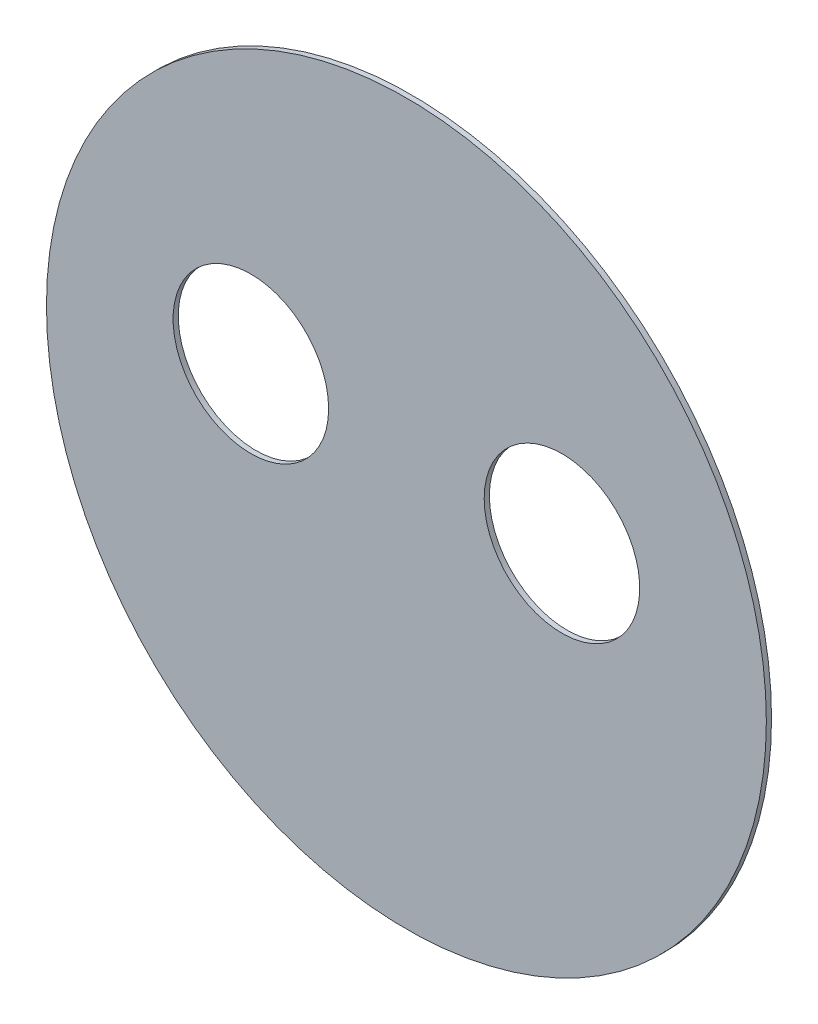
SolidWorks part; units mm, degrees
ref_plane "Front Plane" through (0, 0, 0) normal (0, 0, 1) x (1, 0, 0)
ref_plane "Top Plane" through (0, 0, 0) normal (0, 1, 0) x (1, 0, 0)
ref_plane "Right Plane" through (0, 0, 0) normal (1, 0, 0) x (0, 0, -1)
sketch "Sketch1" plane through (0, 0, 0) normal (0, 0, 1) x (1, 0, 0)
  circle A0 centre (0, 0) radius 34.7111
  dimension "D1" = 69.4222
extrude "Boss-Extrude1" add sketch "Sketch1" along normal blind 0.5 contours A0
sketch "Sketch3" plane through (0, 0, 0.5) normal (0, 0, 1) x (1, 0, 0)
  line L0 (0, 34.7111) -> (0, -34.7111) construction
  line L1 (34.3491, 5) -> (-34.3491, 5) construction
  line L2 (0, 0) -> (-34.7111, 0) construction
  circle A0 centre (0, 0) radius 34.7111 construction
  circle A1 centre (-15, 5) radius 7.5
  circle A2 centre (15, 5) radius 7.5
  dimension "D3" = 15
  dimension "D1" = 5
  dimension "D2" = 15
extrude "Cut-Extrude1" cut sketch "Sketch3" against normal through all
sketch "Sketch4" plane through (0, 0, 0) normal (1, 0, 0) x (0, 0, -1)
  line L0 (0, -2.5) -> (0, 12.5) construction
  line L1 (0, -2.5) -> (0, 12.8039) construction
  line L2 (-0.1452, 5.1519) -> (14.5534, 5.1519) construction
  line L3 (1.5707, 11.6061) -> (0, 5.1519) construction
  line L4 (4, 5.1519) -> (4, 13.9165) construction
  line L5 (2.678, 9.4399) -> (0, 5.1519) construction
  spline S0 degree 3 poles (0, 12.8039) (1.9381, 12.9997) (4, 5.8734) (4, 5.1519) knots 0 0 0 0 1 1 1 1
  point P8 (0, 0)
  dimension "D1" = 4
  dimension "D2" = 6.6426
  dimension "D3" = 1.5707
  dimension "D4" = 5.1519
  dimension "D5" = 5.0555
  dimension "D6" = 4.2879
ref_plane "Plane1" through (15, 0, 0) normal (1, 0, 0) x (0, 0, -1)
